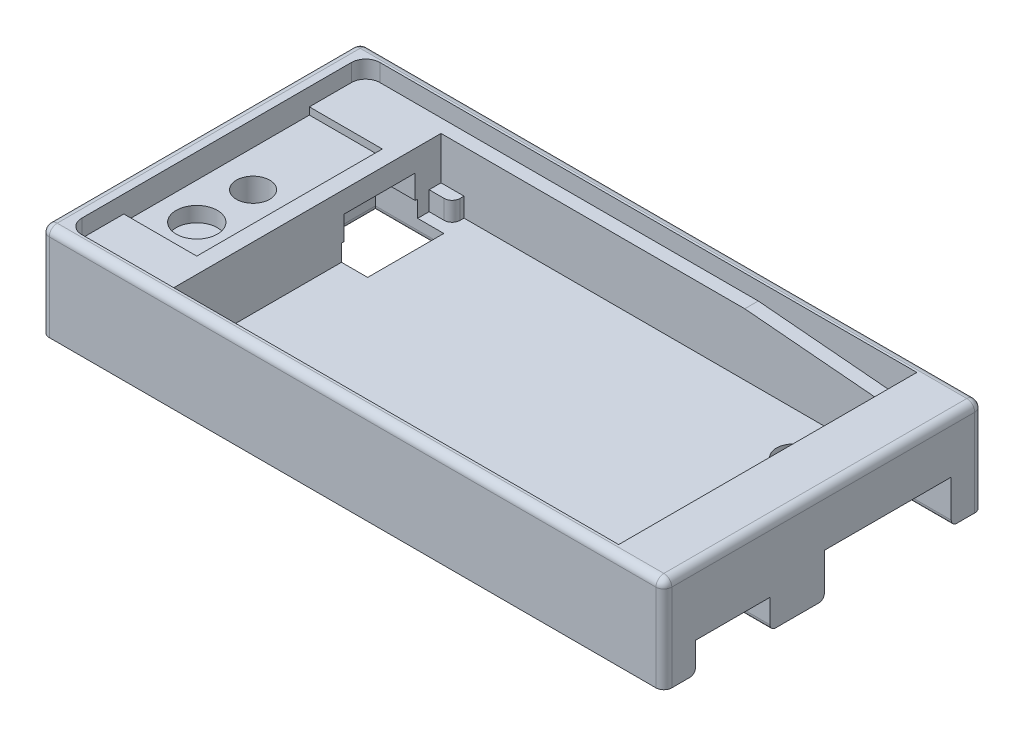
SolidWorks part; units mm, degrees
ref_plane "前视基准面" through (0, 0, 0) normal (0, 0, 1) x (1, 0, 0)
ref_plane "上视基准面" through (0, 0, 0) normal (0, 1, 0) x (1, 0, 0)
ref_plane "右视基准面" through (0, 0, 0) normal (1, 0, 0) x (0, 0, -1)
other "Configuration Table"
sketch "草图1" plane through (0, 0, 0) normal (0, 1, 0) x (1, 0, 0)
  line L0 (-39.25, 0) -> (39.25, 0) construction
  line L1 (-39.25, 20.1) -> (39.25, 20.1)
  line L2 (-39.25, 20.1) -> (-39.25, -20.1)
  line L3 (-39.25, -20.1) -> (39.25, -20.1)
  line L4 (39.25, 20.1) -> (39.25, -20.1)
  line L5 (-39.25, 20.1) -> (39.25, -20.1) construction
  line L6 (-39.25, -20.1) -> (39.25, 20.1) construction
  line L7 (-26.05, -17.1) -> (28.95, -17.1)
  line L8 (-26.05, -17.1) -> (-26.05, 17.1)
  line L9 (-26.05, 17.1) -> (28.95, 17.1)
  line L10 (28.95, -17.1) -> (28.95, 17.1)
  line L12 (32.25, 6.9973) -> (34.45, 6.9973)
  line L13 (32.25, 6.9973) -> (32.25, -6.9973)
  line L14 (32.25, -6.9973) -> (34.45, -6.9973)
  line L15 (34.45, 6.9973) -> (34.45, -6.9973)
  line L16 (-37.25, 18.8) -> (32.25, 18.8)
  line L17 (-37.25, 18.8) -> (-37.25, -18.8)
  line L18 (-37.25, -18.8) -> (32.25, -18.8)
  line L19 (32.25, 18.8) -> (32.25, -18.8)
  circle A0 centre (-32.65, 7.1) radius 2.6
  circle A1 centre (-32.65, 0) radius 2.1
  circle A2 centre (23.75, 11.6973) radius 2.1
  circle A3 centre (23.75, -11.6973) radius 2.1
  circle A4 centre (-32.65, -7.1) radius 2.6
  point P0 (0, 0)
  dimension "D1" = 4.2
  dimension "D6" = 5.2
  dimension "D2" = 5.2
  dimension "D3" = 5.4027
  dimension "D4" = 6.6
  dimension "D5" = 13
  dimension "D7" = 3
  dimension "D8" = 3
  dimension "D9" = 6.6
  dimension "D10" = 10.3
  dimension "D11" = 55
  dimension "D12" = 34.2
  dimension "D13" = 2.2
  dimension "D14" = 4.7
  dimension "D15" = 1.3
  dimension "D16" = 1.3
  dimension "D17" = 2
  dimension "D18" = 7
extrude "凸台-拉伸2" add sketch "草图1" along normal blind 2.2 contours L4 L1 L2 L3 L16 L19 L10 L12 L15 L14 L18 L17 | L15 L12 L10 L14 region at (0, 0, -19.2181) region at (33.35, 0, 0)
extrude "凸台-拉伸3" add sketch "草图1<4>" against normal blind 7.8 contours L19 L16 L17 L18 L7 L8 L9 A0 A1 A4 | L4 L1 L2 L3 L16 L19 L10 L12 L15 L14 L18 L17 | A4 | A0 | A1 | L15 L12 L13 L14 region at (0, 0, -19.2181) region at (33.35, 0, 0) region at (31.4598, 0, 0) region at (-32.65, 0, -7.1) region at (-32.65, 0, 0) region at (-32.65, 0, 7.1)
sketch "草图1<4>" plane through (0, 0, 0) normal (0, 1, 0) x (1, 0, 0) same geometry as "草图1"
sketch "草图2" plane through (0, 0, 0) normal (0, 1, 0) x (1, 0, 0)
  line L0 (-37.25, 18.8) -> (-37.25, -18.8) construction
  line L1 (-37.25, 11.7) -> (-28.05, 11.7)
  line L2 (-37.25, 11.7) -> (-37.25, -11.7)
  line L3 (-37.25, -11.7) -> (-28.05, -11.7)
  line L4 (-28.05, 11.7) -> (-28.05, -11.7)
  circle A0 centre (-32.65, 7.1) radius 2.6 construction
  circle A1 centre (-32.65, 7.1) radius 2.6 construction
  circle A2 centre (-32.65, -7.1) radius 2.6 construction
  circle A3 centre (-32.65, -7.1) radius 2.6 construction
  dimension "D1" = 4.6
  dimension "D2" = 4.6
  dimension "D3" = 4.6
extrude "切除-拉伸1" cut sketch "草图2" against normal blind 0.9
sketch "草图6" plane through (0, -0.9, 0) normal (0, 1, 0) x (1, 0, 0)
  circle A0 centre (-32.65, 7.1) radius 2.6 construction
  circle A1 centre (-32.65, 7.1) radius 2.6
  circle A2 centre (-32.65, -7.1) radius 2.6 construction
  circle A3 centre (-32.65, -7.1) radius 2.6
extrude "切除-拉伸2" cut sketch "草图6" against normal blind 1.9 contours A3 region at (-32.65, -0.9, 7.1)
sketch "草图7" plane through (0, -0.9, 0) normal (0, 1, 0) x (1, 0, 0)
  circle A0 centre (-32.65, 0) radius 2.1 construction
  circle A1 centre (-32.65, 0) radius 2.1
extrude "切除-拉伸3" cut sketch "草图7" against normal blind 1.1
sketch "草图8" plane through (0, -2, 0) normal (0, 1, 0) x (1, 0, 0)
  circle A0 centre (-32.65, 0) radius 1.2
  dimension "2.2" = 2.4
extrude "切除-拉伸4" cut sketch "草图8" against normal through all
sketch "草图9" plane through (0, -7.8, 0) normal (0, -1, 0) x (1, 0, 0)
  line L0 (39.25, -20.1) -> (39.25, 20.1) construction
  line L1 (-39.25, -20.1) -> (39.25, -20.1) construction
  line L2 (-39.25, -20.1) -> (-39.25, 20.1) construction
  line L3 (-39.25, 20.1) -> (39.25, 20.1) construction
  line L4 (39.25, -20.1) -> (39.25, 20.1)
  line L5 (-39.25, -20.1) -> (39.25, -20.1)
  line L6 (-39.25, -20.1) -> (-39.25, 20.1)
  line L7 (-39.25, 20.1) -> (39.25, 20.1)
extrude "凸台-拉伸4" add sketch "草图9" along normal blind 2
sketch "草图10" plane through (0, -7.8, 0) normal (0, 1, 0) x (1, 0, 0)
  circle A0 centre (23.75, -11.6973) radius 2.1 construction
  circle A1 centre (23.75, 11.6973) radius 2.1 construction
  circle A2 centre (23.75, -11.6973) radius 2.1
  circle A3 centre (23.75, 11.6973) radius 2.1
extrude "切除-拉伸5" cut sketch "草图10" against normal blind 1.1
sketch "草图11" plane through (0, -8.9, 0) normal (0, 1, 0) x (1, 0, 0)
  circle A0 centre (23.75, 11.6973) radius 1.2
  circle A1 centre (23.75, -11.6973) radius 1.2
  dimension "D1" = 2.4
  dimension "D2" = 2.4
extrude "切除-拉伸6" cut sketch "草图11" against normal through all
sketch "草图12" plane through (0, -9.8, 0) normal (0, -1, 0) x (1, 0, 0)
  line L0 (-26.05, -17.1) -> (28.95, -17.1) construction
  line L1 (-26.05, -17.1) -> (28.95, -17.1) construction
  line L7 (-30.8239, -4.85) -> (-26.3739, -4.85)
  line L8 (-30.8239, -4.85) -> (-30.8239, -13.85)
  line L9 (-30.8239, -13.85) -> (-26.3739, -13.85)
  line L10 (-26.3739, -4.85) -> (-26.3739, -13.85)
  line L11 (-30.8239, -4.85) -> (-26.3739, -13.85) construction
  line L12 (-30.8239, -13.85) -> (-26.3739, -4.85) construction
  line L13 (-28.5989, -9.35) -> (-23.0895, -9.35) construction
  line L14 (-31.3739, -4.55) -> (-26.3739, -4.55)
  line L15 (-31.3739, -4.55) -> (-31.3739, -14.15)
  line L16 (-31.3739, -14.15) -> (-26.3739, -14.15)
  line L17 (-26.3739, -4.55) -> (-26.3739, -14.15)
  point P6 (-28.5989, -9.35)
  dimension "D1" = 7.75
  dimension "D2" = 4.45
  dimension "D3" = 9
  dimension "D4" = 9.6
  dimension "D5" = 5
extrude "切除-拉伸7" cut sketch "草图12" against normal blind 7.1 contours L10 L7 L8 L9 region at (-28.5989, -9.8, -9.35)
extrude "切除-拉伸8" cut sketch "草图12<3>" against normal offset from surface (4.1 mm away) 3 contours L17 L14 L15 L16 L9 L8 L7 region at (-30.9321, -9.8, -9.35) up to face at (-28.5989, -2.7, -9.35)
sketch "草图12<3>" plane through (0, -9.8, 0) normal (0, -1, 0) x (1, 0, 0) same geometry as "草图12"
sketch "草图13" plane through (-26.3739, 0, 0) normal (-1, 0, 0) x (0, 0, 1)
  line L4 (-4.85, -2.7) -> (-13.85, -2.7)
  line L5 (-4.85, -2.7) -> (-13.85, -2.7)
  line L9 (-13.85, -2.7) -> (-13.85, -5.7)
  line L11 (-13.85, -5.7) -> (-14.15, -5.7)
  line L12 (-14.15, -9.8) -> (-4.55, -9.8)
  line L13 (-13.85, -5.7) -> (-14.15, -5.7)
  line L14 (-14.15, -5.7) -> (-14.15, -9.8)
  line L15 (-4.85, -5.7) -> (-4.85, -2.7)
  line L17 (-13.85, -2.7) -> (-13.85, -5.7)
  line L20 (-14.15, -9.8) -> (-4.55, -9.8)
  line L23 (-4.85, -5.7) -> (-4.85, -2.7)
  line L24 (-14.15, -5.7) -> (-14.15, -9.8)
  line L25 (-4.55, -9.8) -> (-4.55, -5.7)
  line L26 (-4.55, -9.8) -> (-4.55, -5.7)
  line L27 (-4.55, -5.7) -> (-4.85, -5.7)
  line L28 (-4.55, -5.7) -> (-4.85, -5.7)
  dimension "D1" = 0
extrude "切除-拉伸9" cut sketch "草图13" against normal up to surface (0.3239 mm away) up to face at (-26.05, -3.9, 0)
sketch "草图14" plane through (-26.05, 0, 0) normal (-1, 0, 0) x (0, 0, 1)
  line L4 (-14.15, -7.8) -> (-14.15, -9.8)
  line L5 (-14.15, -9.8) -> (-4.55, -9.8)
  line L7 (-4.55, -7.8) -> (-14.15, -7.8)
  line L9 (-14.15, -9.8) -> (-4.55, -9.8)
  line L11 (-4.55, -7.8) -> (-14.15, -7.8)
  line L12 (-14.15, -7.8) -> (-14.15, -9.8)
  line L14 (-4.55, -9.8) -> (-4.55, -7.8)
  line L15 (-4.55, -9.8) -> (-4.55, -7.8)
  dimension "D1" = 0
extrude "切除-拉伸10" cut sketch "草图14" against normal blind 3.3
fillet "圆角1" radius 1.8 4 edges at (32.25, 1.1, 18.8) (32.25, 1.1, -18.8) (-37.25, 1.1, -18.8) (-37.25, 1.1, 18.8)
fillet "圆角2" radius 1 8 edges at (39.25, -3.8, -20.1) (39.25, 2.2, 0) (39.25, -3.8, 20.1) (0, 2.2, -20.1) (-39.25, -3.8, -20.1) (0, 2.2, 20.1) (-39.25, 2.2, 0) (-39.25, -3.8, 20.1)
sketch "草图15" plane through (0, -7.8, 0) normal (0, 1, 0) x (1, 0, 0)
  line L0 (0, 0) -> (25.0264, 0) construction
  line L1 (-26.05, 17.1) -> (-23.15, 17.1)
  line L2 (-26.05, 17.1) -> (-26.05, 15.6)
  line L3 (-26.05, 15.6) -> (-23.15, 15.6)
  line L4 (-23.15, 17.1) -> (-23.15, 15.6)
  line L5 (-26.05, -15.6) -> (-23.15, -15.6)
  line L6 (-23.15, -17.1) -> (-23.15, -15.6)
  line L7 (-26.05, -17.1) -> (-23.15, -17.1)
  line L8 (-26.05, -17.1) -> (-26.05, -15.6)
  dimension "D1" = 2.9
  dimension "D2" = 1.5
extrude "凸台-拉伸5" add sketch "草图15" along normal blind 2.4
sketch "草图16" plane through (0, 0, 0) normal (0, 1, 0) x (1, 0, 0)
  line L0 (0, 0) -> (31.9375, 0) construction
  line L1 (28.95, -17.1) -> (28.95, 17.1) construction
  line L3 (30.2966, 8) -> (30.2966, -8)
  line L4 (32.25, 17) -> (32.25, -17) construction
  line L6 (30.2966, 10.6921) -> (30.2966, 8)
  line L7 (30.2966, -10.6921) -> (30.2966, -8)
  arc A0 (30.2023, 7.5039) -> (30.2966, 10.6921) centre (31.7642, 9.0532) cw
  arc A1 (30.2023, -7.5039) -> (30.2966, -10.6921) centre (31.7642, -9.0532) ccw
  ellipse E0 centre (28.95, 0) end of major axis (28.95, -8.1106) minor radius 3.3 (30.2023, -7.5039) -> (30.2023, 7.5039) ccw
  dimension "D1" = 2.2
revolve "切除-旋转1" [suppressed] cut sketch "草图16" angle 360 about L3
sketch "草图17" plane through (0, -7.8, 0) normal (0, 1, 0) x (1, 0, 0)
  circle A1 centre (-32.65, 0) radius 1.2
  circle A2 centre (-32.65, 0) radius 1.2
  dimension "D1" = 0
extrude "切除-拉伸11" cut sketch "草图17" against normal through all
sketch "草图19" plane through (0, 0, 20.1) normal (0, 0, 1) x (1, 0, 0)
  line L0 (12.25, 0) -> (34.1406, 0.2) construction
  line L1 (32.25, 2.2) -> (30.45, 2.2) construction
  line L2 (12.25, 0) -> (32.25, 2) construction
  line L6 (12.25, 0) -> (12.25, 2)
  line L11 (12.25, 0) -> (34.05, -2) construction
  line L12 (12.25, 0) -> (32.2733, -1.7518)
  line L13 (12.25, 0) -> (33.7215, -4.2678) construction
  line L14 (32.25, 2) -> (32.25, 0) construction
  line L15 (32.25, 0) -> (30.25, 0) construction
  line L17 (12.25, 2) -> (12.25, 3)
  line L18 (12.25, 3) -> (32.25, 3)
  line L19 (32.25, 2) -> (32.25, 3)
  line L20 (32.25, 2.2) -> (30.45, 2.2) construction
  line L21 (-35.45, 0) -> (30.45, 0) construction
  line L22 (-35.45, 0) -> (30.25, 0) construction
  line L23 (12.25, 2) -> (32.25, 2) construction
  line L24 (34.1416, 0) -> (32.3498, 0) construction
  line L25 (30.25, 0) -> (34.05, 0) construction
  line L26 (30.25, 0) -> (30.25, -2) construction
  line L27 (30.25, -2) -> (34.05, -2) construction
  line L28 (34.05, 0) -> (34.05, -2) construction
  line L29 (33.7215, -4.2678) -> (28.7215, -3.2739)
  line L30 (28.7215, -3.2739) -> (28.8807, -1.455)
  line L31 (34.1406, 0.2) -> (32.3489, 0.1836)
  circle A0 centre (12.25, 0) radius 20.0998 construction
  arc A3 (32.25, 2) -> (32.2733, -1.7518) centre (12.25, 0) cw
  circle A4 centre (12.25, 0) radius 21.8916 construction
  arc A5 (33.7215, -4.2678) -> (34.1406, 0.2) centre (12.25, 0) ccw
  line M8 (38.25, 1.2) -> (-38.25, 1.2)
  dimension "D1" = 2
  dimension "D2" = 20
  dimension "D3" = 5
  dimension "D4" = 2
  dimension "D5" = 20
  dimension "D6" = 6
  dimension "D7" = 1
  dimension "D8" = 1.8
  dimension "D9" = 2
  dimension "D10" = 5
  dimension "D11" = 0.2
extrude "切除-拉伸12" cut sketch "草图19" against normal up to surface (38.9 mm away) from surface contours L6 L12 M8 | L6 M8 region at (23.7042, 0.0997, 20.1) region at (22.2577, 2.0995, 20.1) up to face at (-2.5, 1.1, -18.8) starting at face at (-2.5, 1.1, 18.8)
extrude "切除-拉伸13" cut sketch "草图19<3>" against normal up to vertex (27.0973 mm away) from vertex contours L27 L12 L13 region at (31.912, -2.2596, 20.1) up to point (34.45, 0, -6.9973) starting at point (34.45, 0, 6.9973)
sketch "草图19<3>" plane through (0, 0, 20.1) normal (0, 0, 1) x (1, 0, 0) same geometry as "草图19"
sketch "草图20" plane through (0.3556, 2.3642, 0) normal (0.195, 0.9808, 0) x (0.9808, -0.195, 0)
  line L0 (0.1121, 0) -> (29.1537, 0) construction
  line L1 (29.1537, 6.9973) -> (29.1537, -6.9973) construction
  line L2 (29.1537, 6.9973) -> (29.1537, -6.9973) construction
  line L3 (29.1537, 5.3609) -> (29.1537, -5.3609)
  line L4 (29.1537, 0) -> (31.3144, 0) construction
  line L5 (31.3144, 18.8) -> (31.3144, -18.8) construction
  line L6 (29.3869, 4.2263) -> (29.1537, 5.3609) construction
  line L9 (29.1537, -5.3609) -> (29.1537, 5.3609) construction
  ellipse E0 centre (29.1537, 0) end of major axis (29.1537, 5.3609) minor radius 2.1607 (29.1537, 5.3609) -> (29.1537, -5.3609) cw
revolve "切除-旋转2" [suppressed] cut sketch "草图20" angle 360 about L3
fillet "圆角4" [suppressed] radius 1
fillet "圆角5" radius 1 2 edges at (-23.15, -6.6, 15.6) (-23.15, -6.6, -15.6)
sketch "草图21" plane through (0, -2, 0) normal (0, 1, 0) x (1, 0, 0)
  circle A1 centre (-32.65, 0) radius 2.1
  circle A2 centre (-32.65, 0) radius 2.1
  dimension "D1" = 0
extrude "切除-拉伸14" cut sketch "草图21" against normal up to surface (6.9 mm away) up to face at (23.75, -8.9, -10.4973)
sketch "草图22" plane through (0, -9.8, 0) normal (0, -1, 0) x (1, 0, 0)
  line L0 (0, 0) -> (39.25, 0) construction
  line L2 (-39.25, 14.6675) -> (-39.25, 5.2675)
  line L3 (31.35, 16.1208) -> (39.25, 16.1208)
  line L4 (31.35, 16.1208) -> (31.35, 6.7208)
  line L5 (31.35, 6.7208) -> (39.25, 6.7208)
  line L6 (39.25, 16.1208) -> (39.25, 6.7208)
  line L7 (31.35, 16.1208) -> (39.25, 6.7208) construction
  line L8 (31.35, 6.7208) -> (39.25, 16.1208) construction
  line L9 (-39.25, 14.6675) -> (-31.35, 14.6675)
  line L10 (-39.25, 5.2675) -> (-31.35, 5.2675)
  line L11 (-31.35, 14.6675) -> (-31.35, 5.2675)
  line L13 (39.25, -19.1) -> (39.25, 19.1) construction
  line L14 (-39.25, 19.1) -> (-39.25, -19.1) construction
  point P5 (35.3, 11.4208)
  dimension "D1" = 7.9
  dimension "D2" = 9.4
extrude "切除-拉伸15" cut sketch "草图22" against normal blind 3.7
sketch "草图23" plane through (0, -9.8, 0) normal (0, -1, 0) x (1, 0, 0)
  line L1 (39.25, -16.1357) -> (30.85, -16.1357)
  line L2 (39.25, -16.1357) -> (39.25, -0.1357)
  line L3 (39.25, -0.1357) -> (30.85, -0.1357)
  line L4 (30.85, -16.1357) -> (30.85, -0.1357)
  line L6 (32.2733, -18.8) -> (12.25, -18.8) construction
  line L7 (32.2733, -18.8) -> (12.25, -18.8) construction
  line L8 (39.25, -19.1) -> (39.25, 6.7208) construction
  line L9 (39.25, -19.1) -> (39.25, 6.7208) construction
  dimension "D1" = 8.4
  dimension "D2" = 16
extrude "切除-拉伸16" cut sketch "草图23" against normal blind 5.4
fillet "圆角6" radius 0.7 13 edges at (-35.3, -9.8, 5.2675) (35.05, -9.8, -16.1357) (30.85, -9.8, -8.1357) (35.05, -9.8, -0.1357) (35.3, -9.8, 6.7208) (35.3, -9.8, 16.1208) (31.35, -9.8, 11.4208) (-22.75, -9.8, -9.35) (-27.0619, -9.8, -14.15) (-31.3739, -9.8, -9.35) (-27.0619, -9.8, -4.55) (-31.35, -9.8, 9.9675) (-35.3, -9.8, 14.6675)
fillet "圆角7" radius 1 3 edges at (28.95, -2.3902, 6.9973) (28.95, -2.3902, -6.9973) (28.95, -3.3194, 0)
